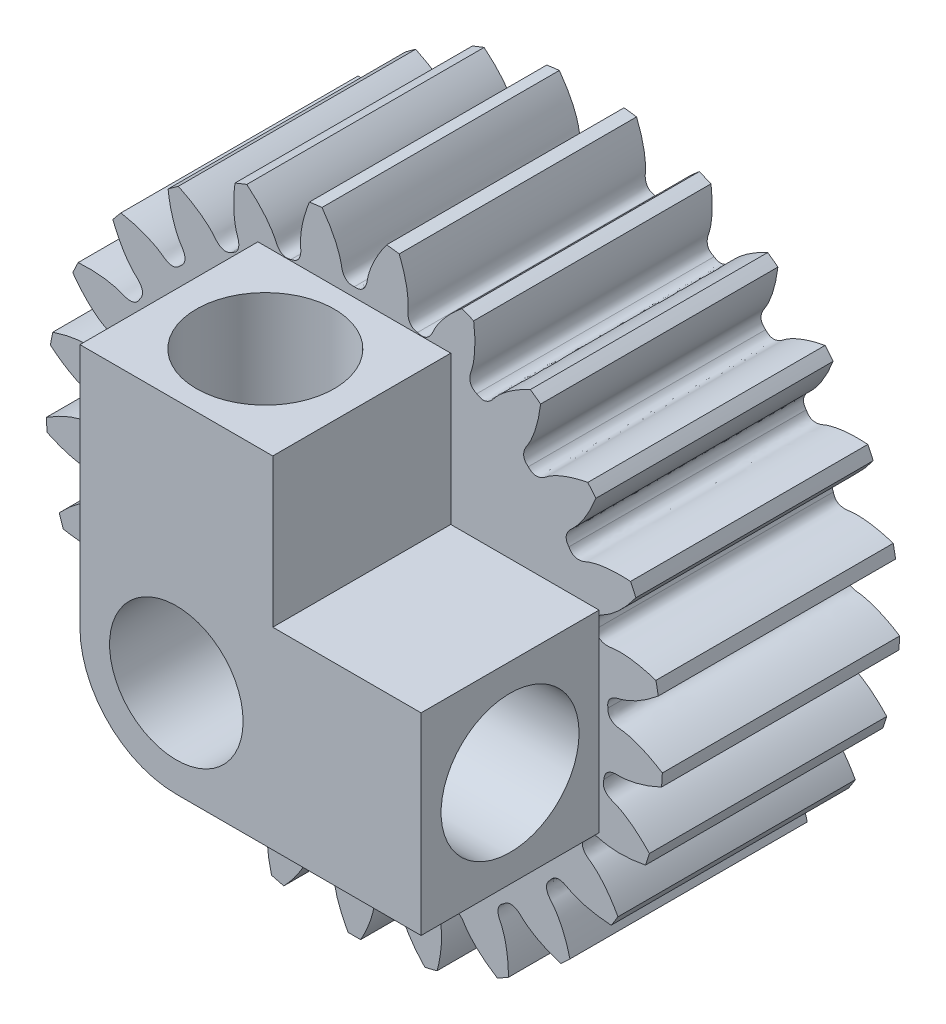
SolidWorks part; units mm, degrees
material "PLA Black"
ref_plane "Front" through (0, 0, 0) normal (0, 0, 1) x (1, 0, 0)
ref_plane "Top" through (0, 0, 0) normal (0, 1, 0) x (1, 0, 0)
ref_plane "Right" through (0, 0, 0) normal (1, 0, 0) x (0, 0, -1)
ref_axis "Axis1" through (0, 0, -15.6032) along (0, 0, 1)
sketch "Gear-BaseSketch" plane through (0, 0, 0) normal (0, 0, 1) x (1, 0, 0)
  circle A0 centre (0, 0) radius 10.3909
  dimension "D1" = 20.7818
extrude "33.0 Diametral Pitch, 20.78mm P.D." add sketch "Gear-BaseSketch" along normal mid plane 8
sketch "Tooth-Sketch; Backlash: 0.0000mm" plane through (0, 0, 0) normal (0, 0, 1) x (1, 0, 0)
  line L0 (0, 0) -> (0, 10.3909) construction
  arc A0 (-1.0905, 10.334) -> (1.0905, 10.334) centre (0, -0.094) cw
  circle A1 centre (0, 0) radius 10.3909 construction
  spline S0 degree 3 poles (-1.0905, 10.334) (-1.0138, 10.2299) (-0.9082, 10.0753) (-0.7851, 9.8689) (-0.7088, 9.729) (-0.6442, 9.5985) (-0.5903, 9.4783) (-0.5464, 9.369) (-0.5115, 9.2711) (-0.4845, 9.1851) (-0.4645, 9.1115) (-0.4506, 9.0507) (-0.4416, 9.0039) (-0.4365, 8.9698) (-0.432, 8.9444) (-0.4246, 8.9083) (-0.4122, 8.8596) (-0.3912, 8.7995) (-0.3638, 8.742) (-0.3272, 8.686) (-0.2761, 8.6321) (-0.1724, 8.5642) (-0.0681, 8.5594) (0, 8.5647) knots 0 0 0 0 0.176711 0.2556 0.328177 0.394444 0.454399 0.508044 0.555377 0.596399 0.63111 0.65951 0.681599 0.696189 0.706616 0.716848 0.746535 0.775185 0.80367 0.83335 0.866218 0.904587 1 1 1 1
  spline S1 degree 3 poles (1.0905, 10.334) (1.0138, 10.2299) (0.9082, 10.0753) (0.7851, 9.8689) (0.7088, 9.729) (0.6442, 9.5985) (0.5903, 9.4783) (0.5464, 9.369) (0.5115, 9.2711) (0.4845, 9.1851) (0.4645, 9.1115) (0.4506, 9.0507) (0.4416, 9.0039) (0.4365, 8.9698) (0.432, 8.9444) (0.4246, 8.9083) (0.4122, 8.8596) (0.3912, 8.7995) (0.3638, 8.742) (0.3272, 8.686) (0.2761, 8.6321) (0.1724, 8.5642) (0.0681, 8.5594) (0, 8.5647) knots 0 0 0 0 0.176711 0.2556 0.328177 0.394444 0.454399 0.508044 0.555377 0.596399 0.63111 0.65951 0.681599 0.696189 0.706616 0.716848 0.746535 0.775185 0.80367 0.83335 0.866218 0.904587 1 1 1 1
extrude "Tooth-Cut, Fine Pitch Involute 20 deg" cut sketch "Tooth-Sketch; Backlash: 0.0000mm" against normal through all and the other way through all
pattern_circular "Tooth Pattern, 25 / 25" count 25 over 360 about axis through (0, 0, -15.6032) along (0, 0, 1) of "Tooth-Cut, Fine Pitch Involute 20 deg"
sketch "Sketch4" plane through (0, 0, 4) normal (0, 0, 1) x (1, 0, 0)
  circle A0 centre (0, 0) radius 2.25
  dimension "D1" = 4.5
extrude "Cut-Extrude2" cut sketch "Sketch4" against normal through all contours A0
sketch "Sketch6" plane through (0, 0, 4) normal (0, 0, 1) x (1, 0, 0)
  circle A0 centre (0, 0) radius 3.25
  circle A1 centre (0, 0) radius 2.25
  circle A2 centre (0, 0) radius 2.25 construction
  dimension "D1" = 6.5
extrude "Boss-Extrude2" add sketch "Sketch6" along normal blind 6
sketch "Sketch9" plane through (0, 0, 4) normal (0, 0, 1) x (1, 0, 0)
  line L0 (-3.25, 0) -> (-3.25, 8.25)
  line L1 (-3.25, 8.25) -> (3.25, 8.25)
  line L2 (3.25, 8.25) -> (3.25, 3.25)
  line L3 (3.25, 3.25) -> (8.25, 3.25)
  line L4 (8.25, 3.25) -> (8.25, -3.25)
  line L5 (8.25, -3.25) -> (0, -3.25)
  circle A0 centre (0, 0) radius 3.25 construction
  circle A1 centre (0, 0) radius 3.25 construction
  arc A2 (-3.25, 0) -> (0, -3.25) centre (0, 0) cw
  dimension "D1" = 5
extrude "Boss-Extrude4" add sketch "Sketch9" along normal through all
ref_plane "Plane1" through (0, 3.25, 0) normal (0, 1, 0) x (1, 0, 0)
sketch "Sketch10" plane through (0, 8.25, 0) normal (0, 1, 0) x (1, 0, 0)
  line L0 (-3.25, -7) -> (3.25, -7) construction
  line L1 (-3.25, -10) -> (-3.25, -4) construction
  line L2 (3.25, -10) -> (3.25, -4) construction
  line L3 (0, -4) -> (0, -10) construction
  line L4 (3.25, -10) -> (-3.25, -10) construction
  circle A0 centre (0, -7) radius 2.325
  dimension "D1" = 4.65
extrude "Cut-Extrude3" cut sketch "Sketch10" against normal blind 8
sketch "Sketch11" plane through (8.25, 0, 0) normal (1, 0, 0) x (0, 0, -1)
  line L0 (-7, 3.25) -> (-7, -3.25) construction
  line L1 (-10, 3.25) -> (-4, 3.25) construction
  line L2 (-10, -3.25) -> (-4, -3.25) construction
  line L3 (-10, 0) -> (-4, -0.4033) construction
  line L4 (-10, -3.25) -> (-10, 3.25) construction
  line L7 (-4, -3.25) -> (-4, 2.4434) construction
  circle A0 centre (-7, 0) radius 2.325
  dimension "D1" = 4.65
extrude "Cut-Extrude4" cut sketch "Sketch11" against normal blind 8 contours A0
